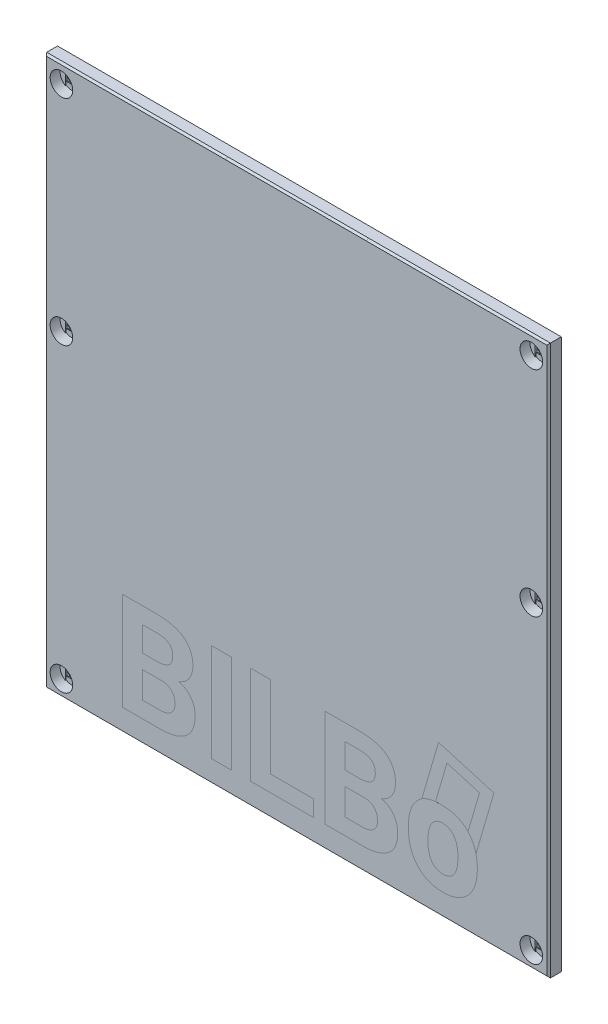
SolidWorks part; units mm, degrees
ref_plane "Front Plane" through (0, 0, 0) normal (0, 0, 1) x (1, 0, 0)
ref_plane "Top Plane" through (0, 0, 0) normal (0, 1, 0) x (1, 0, 0)
ref_plane "Right Plane" through (0, 0, 0) normal (1, 0, 0) x (0, 0, -1)
sketch "Sketch1" plane through (0, 0, 0) normal (0, 0, 1) x (1, 0, 0)
  line L0 (48, -68) -> (-48, -68) construction
  line L1 (56, -32.5) -> (56, -60) construction
  line L2 (56, 46) -> (56, -24.5) construction
  line L3 (-56, -24.5) -> (-56, 46) construction
  line L5 (-15, 54.4) -> (-15, 29) construction
  line L6 (-15, 29) -> (15, 29) construction
  line L7 (15, 29) -> (15, 54) construction
  line L8 (48, 54) -> (15, 54) construction
  line L9 (48, -68) -> (-48, -68) construction
  line L10 (56, -32.5) -> (56, -60) construction
  line L11 (56, 46) -> (56, -24.5) construction
  line L12 (-56, -24.5) -> (-56, 46) construction
  line L13 (-15, 54.4) -> (-48, 54.4) construction
  line L14 (-15, 54.4) -> (-15, 29) construction
  line L15 (-15, 29) -> (15, 29) construction
  line L16 (15, 29) -> (15, 54) construction
  line L17 (48, 54) -> (15, 54) construction
  line L18 (-15.25, 54.05) -> (-15.25, 28.75)
  line L19 (-55.65, 54.05) -> (-15.25, 54.05)
  line L20 (-55.65, 54.05) -> (-55.65, -67.65)
  line L21 (-55.65, -67.65) -> (55.825, -67.65)
  line L22 (55.825, 54.05) -> (55.825, -67.65)
  line L23 (-15.25, 28.75) -> (15.125, 28.75)
  line L24 (15.125, 28.75) -> (15.125, 54.05)
  line L25 (15.125, 54.05) -> (55.825, 54.05)
  circle A0 centre (-52, -64) radius 2.1 construction
  circle A1 centre (-52, 2.6) radius 2.1 construction
  circle A2 centre (52, 2.6) radius 2.1 construction
  circle A3 centre (52, 50) radius 2.1 construction
  circle A4 centre (-52, 50) radius 2.1 construction
  circle A5 centre (-52, -64) radius 2.1 construction
  circle A6 centre (-52, 2.6) radius 2.1 construction
  circle A7 centre (52, 2.6) radius 2.1 construction
  circle A8 centre (52, 50) radius 2.1 construction
  circle A9 centre (-52, 50) radius 2.1 construction
  circle A10 centre (-52, 50) radius 1.35
  circle A11 centre (-52, 2.6) radius 1.35
  circle A12 centre (-52, -64) radius 1.35
  circle A13 centre (52, 50) radius 1.35
  circle A14 centre (52, 2.6) radius 1.35
  circle A15 centre (52, -64) radius 1.35
  dimension "D5" = 2.7
  dimension "D1" = 0.35
  dimension "D2" = 0.35
  dimension "D3" = 0.35
  dimension "D4" = 0.35
  dimension "D6" = 0.25
  dimension "D7" = 0.25
  dimension "D8" = 0.25
extrude "Boss-Extrude1" add sketch "Sketch1" along normal blind 2.8
sketch "Sketch2" plane through (0, 0, 2.8) normal (0, 0, 1) x (1, 0, 0)
  line L5 (15.125, 28.75) -> (-15.25, 28.75) construction
  line L8 (-45.5, -63.25) -> (45.5, -63.25)
  line L9 (-45.5, -63.25) -> (-45.5, 27.75)
  line L10 (-45.5, 27.75) -> (45.5, 27.75)
  line L11 (45.5, -63.25) -> (45.5, 27.75)
  line L31 (-42, 24.25) -> (-28, 24.25)
  line L32 (-42, 24.25) -> (-42, 10.25)
  line L33 (-42, 10.25) -> (-28, 10.25)
  line L34 (-28, 24.25) -> (-28, 10.25)
  line L35 (-28, 24.25) -> (-14, 24.25)
  line L36 (-28, 24.25) -> (-28, 10.25)
  line L37 (-28, 10.25) -> (-14, 10.25)
  line L38 (-14, 24.25) -> (-14, 10.25)
  line L39 (-14, 24.25) -> (0, 24.25)
  line L40 (-14, 24.25) -> (-14, 10.25)
  line L41 (-14, 10.25) -> (0, 10.25)
  line L42 (0, 24.25) -> (0, 10.25)
  line L43 (0, 24.25) -> (14, 24.25)
  line L44 (0, 24.25) -> (0, 10.25)
  line L45 (0, 10.25) -> (14, 10.25)
  line L46 (14, 24.25) -> (14, 10.25)
  line L47 (14, 24.25) -> (28, 24.25)
  line L48 (14, 24.25) -> (14, 10.25)
  line L49 (14, 10.25) -> (28, 10.25)
  line L50 (28, 24.25) -> (28, 10.25)
  line L51 (28, 24.25) -> (42, 24.25)
  line L52 (28, 24.25) -> (28, 10.25)
  line L53 (28, 10.25) -> (42, 10.25)
  line L54 (42, 24.25) -> (42, 10.25)
  line L55 (-42, 10.25) -> (-28, 10.25)
  line L56 (-42, 10.25) -> (-42, -3.75)
  line L57 (-42, -3.75) -> (-28, -3.75)
  line L58 (-28, 10.25) -> (-28, -3.75)
  line L59 (-28, -3.75) -> (-14, -3.75)
  line L60 (-28, -3.75) -> (-28, 10.25)
  line L61 (-28, 10.25) -> (-14, 10.25)
  line L62 (-14, -3.75) -> (-14, 10.25)
  line L63 (-14, -3.75) -> (0, -3.75)
  line L64 (-14, -3.75) -> (-14, 10.25)
  line L65 (-14, 10.25) -> (0, 10.25)
  line L66 (0, -3.75) -> (0, 10.25)
  line L67 (0, -3.75) -> (14, -3.75)
  line L68 (0, -3.75) -> (0, 10.25)
  line L69 (0, 10.25) -> (14, 10.25)
  line L70 (14, -3.75) -> (14, 10.25)
  line L71 (14, -3.75) -> (28, -3.75)
  line L72 (14, -3.75) -> (14, 10.25)
  line L73 (14, 10.25) -> (28, 10.25)
  line L74 (28, -3.75) -> (28, 10.25)
  line L75 (28, -3.75) -> (42, -3.75)
  line L76 (28, -3.75) -> (28, 10.25)
  line L77 (28, 10.25) -> (42, 10.25)
  line L78 (42, -3.75) -> (42, 10.25)
  line L79 (42, -3.75) -> (28, -3.75)
  line L80 (42, -3.75) -> (42, -17.75)
  line L81 (42, -17.75) -> (28, -17.75)
  line L82 (28, -3.75) -> (28, -17.75)
  line L83 (14, -3.75) -> (28, -3.75)
  line L84 (14, -3.75) -> (14, -17.75)
  line L85 (14, -17.75) -> (28, -17.75)
  line L86 (28, -3.75) -> (28, -17.75)
  line L87 (0, -3.75) -> (14, -3.75)
  line L88 (0, -3.75) -> (0, -17.75)
  line L89 (0, -17.75) -> (14, -17.75)
  line L90 (14, -3.75) -> (14, -17.75)
  line L91 (-14, -3.75) -> (0, -3.75)
  line L92 (-14, -3.75) -> (-14, -17.75)
  line L93 (-14, -17.75) -> (0, -17.75)
  line L94 (0, -3.75) -> (0, -17.75)
  line L95 (-28, -3.75) -> (-14, -3.75)
  line L96 (-28, -3.75) -> (-28, -17.75)
  line L97 (-28, -17.75) -> (-14, -17.75)
  line L98 (-14, -3.75) -> (-14, -17.75)
  line L99 (-42, -3.75) -> (-28, -3.75)
  line L100 (-42, -3.75) -> (-42, -17.75)
  line L101 (-42, -17.75) -> (-28, -17.75)
  line L102 (-28, -3.75) -> (-28, -17.75)
  line L103 (-42, -17.75) -> (-28, -17.75)
  line L104 (-42, -17.75) -> (-42, -31.75)
  line L105 (-42, -31.75) -> (-28, -31.75)
  line L106 (-28, -17.75) -> (-28, -31.75)
  line L107 (-28, -31.75) -> (-14, -31.75)
  line L108 (-28, -31.75) -> (-28, -17.75)
  line L109 (-28, -17.75) -> (-14, -17.75)
  line L110 (-14, -31.75) -> (-14, -17.75)
  line L111 (-14, -17.75) -> (0, -17.75)
  line L112 (-14, -17.75) -> (-14, -31.75)
  line L113 (-14, -31.75) -> (0, -31.75)
  line L114 (0, -17.75) -> (0, -31.75)
  line L115 (0, -31.75) -> (14, -31.75)
  line L116 (0, -31.75) -> (0, -17.75)
  line L117 (0, -17.75) -> (14, -17.75)
  line L118 (14, -31.75) -> (14, -17.75)
  line L119 (14, -31.75) -> (28, -31.75)
  line L120 (14, -31.75) -> (14, -17.75)
  line L121 (14, -17.75) -> (28, -17.75)
  line L122 (28, -31.75) -> (28, -17.75)
  line L123 (28, -31.75) -> (42, -31.75)
  line L124 (28, -31.75) -> (28, -17.75)
  line L125 (28, -17.75) -> (42, -17.75)
  line L126 (42, -31.75) -> (42, -17.75)
  line L127 (-42, -31.75) -> (-28, -31.75)
  line L128 (-42, -31.75) -> (-42, -45.75)
  line L129 (-42, -45.75) -> (-28, -45.75)
  line L130 (-28, -31.75) -> (-28, -45.75)
  line L131 (-28, -45.75) -> (-14, -45.75)
  line L132 (-28, -45.75) -> (-28, -31.75)
  line L133 (-28, -31.75) -> (-14, -31.75)
  line L134 (-14, -45.75) -> (-14, -31.75)
  line L135 (-14, -45.75) -> (0, -45.75)
  line L136 (-14, -45.75) -> (-14, -31.75)
  line L137 (-14, -31.75) -> (0, -31.75)
  line L138 (0, -45.75) -> (0, -31.75)
  line L139 (0, -45.75) -> (14, -45.75)
  line L140 (0, -45.75) -> (0, -31.75)
  line L141 (0, -31.75) -> (14, -31.75)
  line L142 (14, -45.75) -> (14, -31.75)
  line L143 (14, -45.75) -> (28, -45.75)
  line L144 (14, -45.75) -> (14, -31.75)
  line L145 (14, -31.75) -> (28, -31.75)
  line L146 (28, -45.75) -> (28, -31.75)
  line L147 (28, -45.75) -> (42, -45.75)
  line L148 (28, -45.75) -> (28, -31.75)
  line L149 (28, -31.75) -> (42, -31.75)
  line L150 (42, -45.75) -> (42, -31.75)
  line L151 (42, -45.75) -> (28, -45.75)
  line L152 (42, -45.75) -> (42, -59.75)
  line L153 (42, -59.75) -> (28, -59.75)
  line L154 (28, -45.75) -> (28, -59.75)
  line L155 (28, -59.75) -> (14, -59.75)
  line L156 (28, -59.75) -> (28, -45.75)
  line L157 (28, -45.75) -> (14, -45.75)
  line L158 (14, -59.75) -> (14, -45.75)
  line L159 (0, -45.75) -> (14, -45.75)
  line L160 (0, -45.75) -> (0, -59.75)
  line L161 (0, -59.75) -> (14, -59.75)
  line L162 (14, -45.75) -> (14, -59.75)
  line L163 (-14, -45.75) -> (0, -45.75)
  line L164 (-14, -45.75) -> (-14, -59.75)
  line L165 (-14, -59.75) -> (0, -59.75)
  line L166 (0, -45.75) -> (0, -59.75)
  line L167 (-28, -45.75) -> (-14, -45.75)
  line L168 (-28, -45.75) -> (-28, -59.75)
  line L169 (-28, -59.75) -> (-14, -59.75)
  line L170 (-14, -45.75) -> (-14, -59.75)
  line L171 (-42, -45.75) -> (-28, -45.75)
  line L172 (-42, -45.75) -> (-42, -59.75)
  line L173 (-42, -59.75) -> (-28, -59.75)
  line L174 (-28, -45.75) -> (-28, -59.75)
  point P3 (0, 27.75)
  point P58 (-45.5, -17.75)
  dimension "D1" = 1
  dimension "D2" = 91
  dimension "D3" = 14
sketch "Sketch3" plane through (0, 0, 2.8) normal (0, 0, 1) x (1, 0, 0)
  circle A0 centre (-52, 50) radius 2.5
  circle A1 centre (-52, 2.6) radius 2.5
  circle A2 centre (-52, -64) radius 2.5
  circle A3 centre (52, -64) radius 2.5
  circle A4 centre (52, 2.6) radius 2.5
  circle A5 centre (52, 50) radius 2.5
  dimension "D1" = 5
extrude "Cut-Extrude1" cut sketch "Sketch3" against normal blind 2.2
sketch "Sketch4" plane through (0, 0, 0) normal (0, 0, -1) x (-1, 0, 0)
  line L0 (-15.125, 28.75) -> (15.25, 28.75) construction
  line L1 (-45.65, -57.65) -> (45.65, -57.65)
  line L2 (-45.65, -57.65) -> (-45.65, 27.75)
  line L3 (-45.65, 27.75) -> (45.65, 27.75)
  line L4 (45.65, -57.65) -> (45.65, 27.75)
  line L5 (-45.65, -57.65) -> (45.65, 27.75) construction
  line L6 (-45.65, 27.75) -> (45.65, -57.65) construction
  line L7 (55.65, 54.05) -> (55.65, -67.65) construction
  line L8 (55.65, -67.65) -> (-55.825, -67.65) construction
  point P0 (0, -14.95)
  point P9 (0, 27.75)
  dimension "D1" = 1
  dimension "D2" = 10
  dimension "D3" = 10
extrude "Cut-Extrude2" cut sketch "Sketch4" against normal blind 1.5
sketch "Sketch5" plane through (0, 0, 0.6) normal (0, 0, 1) x (1, 0, 0)
  line L2 (-53.35, 47.8958) -> (-53.35, 52.1042)
  line L4 (-50.65, 47.8958) -> (-50.65, 52.1042)
  line L5 (-53.35, 47.8958) -> (-50.65, 52.1042) construction
  line L6 (-53.35, 52.1042) -> (-50.65, 47.8958) construction
  line L8 (-53.35, 0.4958) -> (-53.35, 4.7042)
  line L10 (-50.65, 0.4958) -> (-50.65, 4.7042)
  line L11 (-53.35, 0.4958) -> (-50.65, 4.7042) construction
  line L12 (-53.35, 4.7042) -> (-50.65, 0.4958) construction
  line L14 (-53.35, -66.1042) -> (-53.35, -61.8958)
  line L16 (-50.65, -66.1042) -> (-50.65, -61.8958)
  line L17 (-53.35, -66.1042) -> (-50.65, -61.8958) construction
  line L18 (-53.35, -61.8958) -> (-50.65, -66.1042) construction
  circle A0 centre (-52, 50) radius 2.5 construction
  circle A1 centre (-52, 50) radius 1.35 construction
  arc A2 (-50.65, 52.1042) -> (-53.35, 52.1042) centre (-52, 50) ccw
  arc A3 (-53.35, 47.8958) -> (-50.65, 47.8958) centre (-52, 50) ccw
  circle A4 centre (-52, 2.6) radius 2.5 construction
  circle A5 centre (-52, 2.6) radius 1.35 construction
  circle A6 centre (-52, 2.6) radius 2.5 construction
  arc A7 (-50.65, 4.7042) -> (-53.35, 4.7042) centre (-52, 2.6) ccw
  arc A8 (-53.35, 0.4958) -> (-50.65, 0.4958) centre (-52, 2.6) ccw
  circle A9 centre (-52, -64) radius 2.5 construction
  circle A10 centre (-52, -64) radius 1.35 construction
  circle A11 centre (-52, -64) radius 2.5 construction
  arc A12 (-50.65, -61.8958) -> (-53.35, -61.8958) centre (-52, -64) ccw
  arc A13 (-53.35, -66.1042) -> (-50.65, -66.1042) centre (-52, -64) ccw
  point P0 (-52, 50)
  point P10 (-52, 2.6)
  point P22 (-52, -64)
extrude "Cut-Extrude3" cut sketch "Sketch5" against normal blind 0.2
sketch "Sketch6" plane through (0, 0, 0.4) normal (0, 0, 1) x (1, 0, 0)
  line L0 (-50.65, -66.1042) -> (-50.65, -61.8958) construction
  line L1 (-53.35, -65.35) -> (-50.65, -65.35)
  line L2 (-53.35, -65.35) -> (-53.35, -62.65)
  line L3 (-53.35, -62.65) -> (-50.65, -62.65)
  line L4 (-50.65, -65.35) -> (-50.65, -62.65)
  line L5 (-53.35, -65.35) -> (-50.65, -62.65) construction
  line L6 (-53.35, -62.65) -> (-50.65, -65.35) construction
  line L7 (-50.65, 0.4958) -> (-50.65, 4.7042) construction
  line L8 (-53.35, 1.25) -> (-50.65, 1.25)
  line L9 (-53.35, 1.25) -> (-53.35, 3.95)
  line L10 (-53.35, 3.95) -> (-50.65, 3.95)
  line L11 (-50.65, 1.25) -> (-50.65, 3.95)
  line L12 (-53.35, 1.25) -> (-50.65, 3.95) construction
  line L13 (-53.35, 3.95) -> (-50.65, 1.25) construction
  line L14 (-50.65, 47.8958) -> (-50.65, 52.1042) construction
  line L15 (-53.35, 48.65) -> (-50.65, 48.65)
  line L16 (-53.35, 48.65) -> (-53.35, 51.35)
  line L17 (-53.35, 51.35) -> (-50.65, 51.35)
  line L18 (-50.65, 48.65) -> (-50.65, 51.35)
  line L19 (-53.35, 48.65) -> (-50.65, 51.35) construction
  line L20 (-53.35, 51.35) -> (-50.65, 48.65) construction
  arc A0 (-50.65, -64) -> (-53.35, -64) centre (-52, -64) ccw construction
  arc A1 (-50.65, 2.6) -> (-53.35, 2.6) centre (-52, 2.6) ccw construction
  arc A2 (-50.65, 50) -> (-53.35, 50) centre (-52, 50) ccw construction
  point P0 (-52, -64)
  point P11 (-52, 2.6)
  point P22 (-52, 50)
extrude "Cut-Extrude4" cut sketch "Sketch6" against normal blind 0.2
mirror "Mirror1" about plane through (0, 0, 0) normal (1, 0, 0) of "Cut-Extrude4", "Cut-Extrude3"
chamfer "Chamfer1" distance 0.4 angle 45 8 edges at (0.0875, -67.65, 2.8) (55.825, -6.8, 2.8) (35.475, 54.05, 2.8) (15.125, 41.4, 2.8) (-0.0625, 28.75, 2.8) (-15.25, 41.4, 2.8) (-35.45, 54.05, 2.8) (-55.65, -6.8, 2.8)
sketch "Sketch11" plane through (0, 0, 2.8) normal (0, 0, 1) x (1, 0, 0)
  line L0 (15.125, 54.05) -> (55.825, 54.05) construction
  line L1 (-15.65, 28.35) -> (15.525, 28.35)
  line L2 (-15.65, 28.35) -> (-15.65, 54.05)
  line L3 (-15.65, 54.05) -> (15.525, 54.05)
  line L4 (15.525, 28.35) -> (15.525, 54.05)
  line L5 (15.525, 53.65) -> (15.525, 28.35) construction
extrude "Boss-Extrude4" add sketch "Sketch11" against normal up to surface (2.8 mm away) up to face at (0, -14.95, 0)
chamfer "Chamfer2" distance 0.4 angle 45 1 edges at (-0.0625, 54.05, 2.8)
sketch "Sketch13" plane through (0, 0, 2.8) normal (0, 0, 1) x (1, 0, 0)
  line L0 (31.4653, -34.4586) -> (43.7332, -38.0443)
  line L1 (43.7332, -38.0443) -> (39.7477, -51.6803)
  line L6 (27.7668, -47.1124) -> (31.4653, -34.4586)
  line L7 (-38.5158, -62.7134) -> (-38.5158, -41.0445)
  line L8 (-38.5158, -41.0445) -> (-30.9257, -41.0445)
  line L9 (-30.0923, -62.7134) -> (-38.5158, -62.7134)
  line L10 (-34.051, -53.2779) -> (-34.051, -59.1267)
  line L11 (-34.051, -59.1267) -> (-30.2263, -59.1267)
  line L12 (-29.9584, -53.2779) -> (-34.051, -53.2779)
  line L13 (-34.051, -50.1228) -> (-30.7471, -50.1228)
  line L14 (-30.9257, -44.661) -> (-34.051, -44.661)
  line L15 (-34.051, -44.661) -> (-34.051, -50.1228)
  line L16 (-14.3169, -62.7134) -> (-18.7817, -62.7134)
  line L17 (-18.7817, -62.7134) -> (-18.7817, -41.0445)
  line L18 (-18.7817, -41.0445) -> (-14.3169, -41.0445)
  line L19 (-14.3169, -41.0445) -> (-14.3169, -62.7134)
  line L20 (-5.7149, -59.1267) -> (3.7652, -59.1267)
  line L21 (3.7652, -59.1267) -> (3.7652, -62.7134)
  line L22 (3.7652, -62.7134) -> (-10.1796, -62.7134)
  line L23 (-10.1796, -62.7134) -> (-10.1796, -41.0445)
  line L24 (-10.1796, -41.0445) -> (-5.7149, -41.0445)
  line L25 (-5.7149, -41.0445) -> (-5.7149, -59.1267)
  line L26 (6.325, -62.7134) -> (6.325, -41.0445)
  line L27 (6.325, -41.0445) -> (13.9151, -41.0445)
  line L28 (14.7485, -62.7134) -> (6.325, -62.7134)
  line L29 (10.7897, -53.2779) -> (10.7897, -59.1267)
  line L30 (10.7897, -59.1267) -> (14.6145, -59.1267)
  line L31 (14.8824, -53.2779) -> (10.7897, -53.2779)
  line L32 (10.7897, -50.1228) -> (14.0936, -50.1228)
  line L33 (13.9151, -44.661) -> (10.7897, -44.661)
  line L34 (10.7897, -44.661) -> (10.7897, -50.1228)
  line L35 (40.0488, -54.4805) -> (40.0611, -54.528)
  line L36 (24.8066, -54.409) -> (24.8065, -54.1022)
  line L37 (30.7951, -46.1553) -> (33.3258, -37.4967)
  line L38 (33.3258, -37.4967) -> (40.5294, -39.6022)
  line L39 (40.5294, -39.6022) -> (37.9924, -48.2821)
  line L40 (33.3258, -37.4967) -> (30.7936, -36.7566) construction
  line L41 (40.5294, -39.6022) -> (43.0616, -40.3423) construction
  spline S0 degree 3 poles (-30.9257, -41.0445) (-28.2965, -41.0445) (-26.3023, -41.5505) (-24.943, -42.5625) knots 0 0 0 0 1 1 1 1
  spline S1 degree 3 poles (-24.943, -42.5625) (-23.5837, -43.5646) (-22.9041, -45.038) (-22.9041, -46.9826) knots 0 0 0 0 1 1 1 1
  spline S2 degree 3 poles (-22.9041, -46.9826) (-22.9041, -48.0443) (-23.1769, -48.9818) (-23.7226, -49.7954) knots 0 0 0 0 1 1 1 1
  spline S3 degree 3 poles (-23.7226, -49.7954) (-24.2683, -50.5991) (-25.0273, -51.1894) (-25.9996, -51.5664) knots 0 0 0 0 1 1 1 1
  spline S4 degree 3 poles (-25.9996, -51.5664) (-24.8884, -51.8442) (-24.0153, -52.4048) (-23.3803, -53.2481) knots 0 0 0 0 1 1 1 1
  spline S5 degree 3 poles (-23.3803, -53.2481) (-22.7354, -54.0915) (-22.413, -55.1233) (-22.413, -56.3437) knots 0 0 0 0 1 1 1 1
  spline S6 degree 3 poles (-22.413, -56.3437) (-22.413, -58.4272) (-23.0777, -60.0048) (-24.4072, -61.0763) knots 0 0 0 0 1 1 1 1
  spline S7 degree 3 poles (-24.4072, -61.0763) (-25.7367, -62.1478) (-27.6317, -62.6935) (-30.0923, -62.7134) knots 0 0 0 0 1 1 1 1
  spline S8 degree 3 poles (-30.2263, -59.1267) (-29.1746, -59.1267) (-28.356, -58.8787) (-27.7707, -58.3826) knots 0 0 0 0 1 1 1 1
  spline S9 degree 3 poles (-27.7707, -58.3826) (-27.1754, -57.8766) (-26.8777, -57.1821) (-26.8777, -56.299) knots 0 0 0 0 1 1 1 1
  spline S10 degree 3 poles (-26.8777, -56.299) (-26.8777, -54.3147) (-27.9046, -53.3077) (-29.9584, -53.2779) knots 0 0 0 0 1 1 1 1
  spline S11 degree 3 poles (-30.7471, -50.1228) (-28.4949, -50.0831) (-27.3688, -49.1852) (-27.3688, -47.4291) knots 0 0 0 0 1 1 1 1
  spline S12 degree 3 poles (-27.3688, -47.4291) (-27.3688, -46.4469) (-27.6566, -45.7424) (-28.232, -45.3158) knots 0 0 0 0 1 1 1 1
  spline S13 degree 3 poles (-28.232, -45.3158) (-28.7975, -44.8793) (-29.6954, -44.661) (-30.9257, -44.661) knots 0 0 0 0 1 1 1 1
  spline S14 degree 3 poles (13.9151, -41.0445) (16.5443, -41.0445) (18.5385, -41.5505) (19.8978, -42.5625) knots 0 0 0 0 1 1 1 1
  spline S15 degree 3 poles (19.8978, -42.5625) (21.2571, -43.5646) (21.9367, -45.038) (21.9367, -46.9826) knots 0 0 0 0 1 1 1 1
  spline S16 degree 3 poles (21.9367, -46.9826) (21.9367, -48.0443) (21.6638, -48.9818) (21.1182, -49.7954) knots 0 0 0 0 1 1 1 1
  spline S17 degree 3 poles (21.1182, -49.7954) (20.5725, -50.5991) (19.8135, -51.1894) (18.8411, -51.5664) knots 0 0 0 0 1 1 1 1
  spline S18 degree 3 poles (18.8411, -51.5664) (19.9524, -51.8442) (20.8255, -52.4048) (21.4605, -53.2481) knots 0 0 0 0 1 1 1 1
  spline S19 degree 3 poles (21.4605, -53.2481) (22.1054, -54.0915) (22.4278, -55.1233) (22.4278, -56.3437) knots 0 0 0 0 1 1 1 1
  spline S20 degree 3 poles (22.4278, -56.3437) (22.4278, -58.4272) (21.7631, -60.0048) (20.4336, -61.0763) knots 0 0 0 0 1 1 1 1
  spline S21 degree 3 poles (20.4336, -61.0763) (19.1041, -62.1478) (17.209, -62.6935) (14.7485, -62.7134) knots 0 0 0 0 1 1 1 1
  spline S22 degree 3 poles (14.6145, -59.1267) (15.6662, -59.1267) (16.4848, -58.8787) (17.0701, -58.3826) knots 0 0 0 0 1 1 1 1
  spline S23 degree 3 poles (17.0701, -58.3826) (17.6654, -57.8766) (17.9631, -57.1821) (17.9631, -56.299) knots 0 0 0 0 1 1 1 1
  spline S24 degree 3 poles (17.9631, -56.299) (17.9631, -54.3147) (16.9362, -53.3077) (14.8824, -53.2779) knots 0 0 0 0 1 1 1 1
  spline S25 degree 3 poles (14.0936, -50.1228) (16.3459, -50.0831) (17.472, -49.1852) (17.472, -47.4291) knots 0 0 0 0 1 1 1 1
  spline S26 degree 3 poles (17.472, -47.4291) (17.472, -46.4469) (17.1842, -45.7424) (16.6088, -45.3158) knots 0 0 0 0 1 1 1 1
  spline S27 degree 3 poles (16.6088, -45.3158) (16.0432, -44.8793) (15.1453, -44.661) (13.9151, -44.661) knots 0 0 0 0 1 1 1 1
  spline S28 degree 3 poles (24.8065, -54.1022) (24.7382, -52.5063) (24.9846, -51.0707) (25.5458, -49.7954) knots 0 0 0 0 1 1 1 1
  spline S29 degree 3 poles (25.5458, -49.7954) (26.1203, -48.5639) (26.9618, -47.6027) (28.0703, -46.9118) knots 0 0 0 0 1 1 1 1
  spline S30 degree 3 poles (28.0703, -46.9118) (29.4511, -46.2514) (31.0058, -45.9963) (32.7346, -46.1465) knots 0 0 0 0 1 1 1 1
  spline S31 degree 3 poles (32.7346, -46.1465) (34.9067, -46.2046) (36.6593, -46.9165) (37.9924, -48.2821) knots 0 0 0 0 1 1 1 1
  spline S32 degree 3 poles (37.9924, -48.2821) (39.3958, -49.8774) (40.0813, -51.9435) (40.0488, -54.4805) knots 0 0 0 0 1 1 1 1
  spline S33 degree 3 poles (40.0611, -54.528) (40.0611, -56.9985) (39.3716, -58.9828) (37.9924, -60.481) knots 0 0 0 0 1 1 1 1
  spline S34 degree 3 poles (37.9924, -60.481) (36.6133, -61.9693) (34.7629, -62.7134) (32.4413, -62.7134) knots 0 0 0 0 1 1 1 1
  spline S35 degree 3 poles (32.4413, -62.7134) (30.1196, -62.7134) (28.2643, -61.9693) (26.8753, -60.481) knots 0 0 0 0 1 1 1 1
  spline S36 degree 3 poles (26.8753, -60.481) (25.4961, -58.9928) (24.8066, -56.9688) (24.8066, -54.409) knots 0 0 0 0 1 1 1 1
  spline S37 degree 3 poles (29.1076, -54.528) (29.1076, -56.056) (29.3953, -57.2267) (29.9707, -58.0403) knots 0 0 0 0 1 1 1 1
  spline S38 degree 3 poles (29.9707, -58.0403) (30.5462, -58.8439) (31.3697, -59.2458) (32.4412, -59.2458) knots 0 0 0 0 1 1 1 1
  spline S39 degree 3 poles (32.4412, -59.2458) (33.483, -59.2458) (34.2966, -58.8489) (34.8819, -58.0552) knots 0 0 0 0 1 1 1 1
  spline S40 degree 3 poles (34.8819, -58.0552) (35.4673, -57.2515) (35.76, -55.9716) (35.76, -54.2155) knots 0 0 0 0 1 1 1 1
  spline S41 degree 3 poles (35.76, -54.2155) (35.76, -52.7173) (35.4673, -51.5565) (34.8819, -50.733) knots 0 0 0 0 1 1 1 1
  spline S42 degree 3 poles (34.8819, -50.733) (34.2966, -49.9095) (33.4731, -49.4978) (32.4115, -49.4978) knots 0 0 0 0 1 1 1 1
  spline S43 degree 3 poles (32.4115, -49.4978) (31.3598, -49.4978) (30.5462, -49.9095) (29.9707, -50.733) knots 0 0 0 0 1 1 1 1
  spline S44 degree 3 poles (29.9707, -50.733) (29.3953, -51.5466) (29.1076, -52.8116) (29.1076, -54.528) knots 0 0 0 0 1 1 1 1
  point P83 (40.0488, -54.4805)
  point P85 (25.5458, -49.7954)
extrude "Cut-Extrude5" cut sketch "Sketch13" against normal blind 0.6 contours S7 S6 S5 S4 S3 S2 S1 S0 L8 L7 L9 S13 S12 S11 L13 L15 L14 S10 S9 S8 L11 L10 L12 | L19 L18 L17 L16 | L25 L24 L23 L22 L21 L20 | S21 S20 S19 S18 S17 S16 S15 S14 L27 L26 L28 S27 S26 S25 L32 L34 L33 S24 S23 S22 L30 L29 L31 | S36 S35 S34 S33 L35 S32 S31 S30 S29 S28 L36 S44 S43 S42 S41 S40 S39 S38 S37 region at (28.0416, -47.1983, 2.8) region at (-31.1653, -51.9214, 2.8) region at (-16.5493, -51.879, 2.8) region at (-6.134, -54.2302, 2.8) region at (13.6755, -51.9214, 2.8)
extrude "Boss-Extrude6" add sketch "Sketch13<4>" against normal up to surface (0.6 mm away) separate body contours S7 S6 S5 S4 S3 S2 S1 S0 L8 L7 L9 S13 S12 S11 L13 L15 L14 S10 S9 S8 L11 L10 L12 | L19 L18 L17 L16 | L25 L24 L23 L22 L21 L20 | S21 S20 S19 S18 S17 S16 S15 S14 L27 L26 L28 S27 S26 S25 L32 L34 L33 S24 S23 S22 L30 L29 L31 | S36 S35 S34 S33 L35 S32 S31 S30 S29 S28 L36 S44 S43 S42 S41 S40 S39 S38 S37 region at (28.0416, -47.1983, 2.8) region at (-31.1653, -51.9214, 2.8) region at (-16.5493, -51.879, 2.8) region at (-6.134, -54.2302, 2.8) region at (13.6755, -51.9214, 2.8) up to face at (-30.8811, -47.5072, 2.2)
sketch "Sketch13<4>" plane through (0, 0, 2.8) normal (0, 0, 1) x (1, 0, 0) same geometry as "Sketch13"
extrude "Cut-Extrude6" cut sketch "Sketch13<5>" against normal blind 0.6 contours S31 S32 L1 L0 L6 S29 S30 region at (37.5334, -36.4769, 2.8)
sketch "Sketch13<5>" plane through (0, 0, 2.8) normal (0, 0, 1) x (1, 0, 0) same geometry as "Sketch13"
extrude "Boss-Extrude7" add sketch "Sketch13<6>" against normal up to surface (0.6 mm away) separate body contours S31 S32 L1 L0 L6 S29 S30 region at (37.5334, -36.4769, 2.8) up to face at (34.1027, -44.1898, 2.2)
sketch "Sketch13<6>" plane through (0, 0, 2.8) normal (0, 0, 1) x (1, 0, 0) same geometry as "Sketch13"
